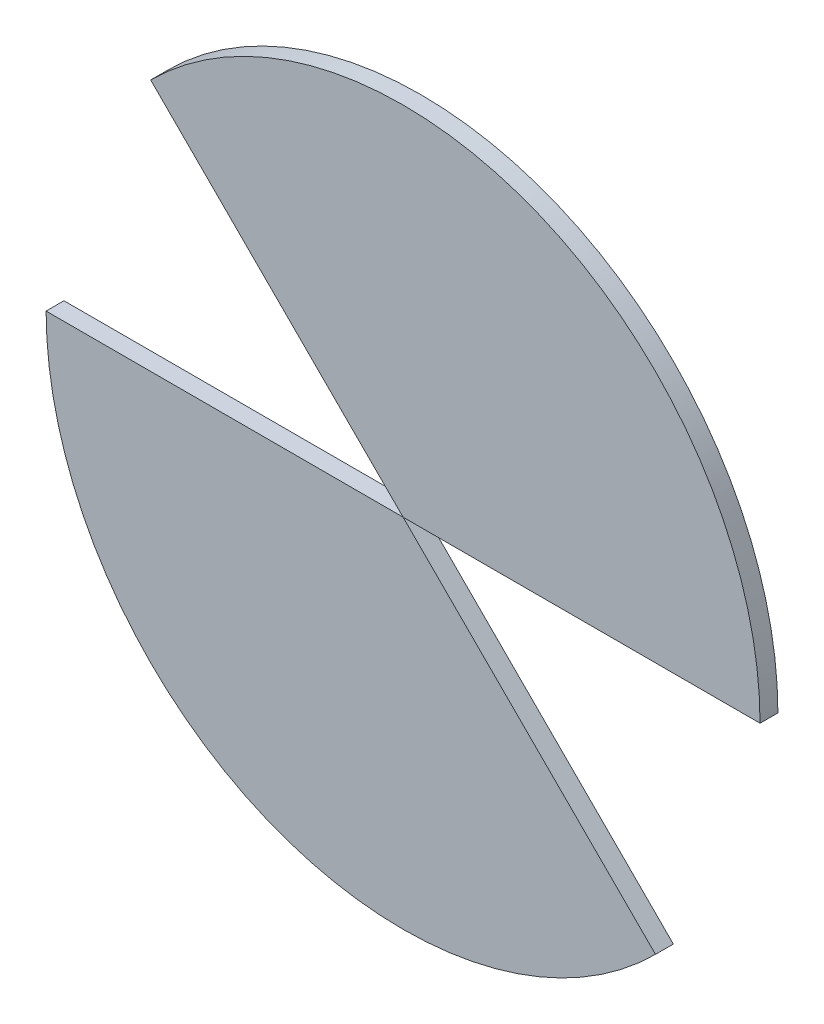
SolidWorks part; units mm, degrees
ref_plane "Front Plane" through (0, 0, 0) normal (0, 0, 1) x (1, 0, 0)
ref_plane "Top Plane" through (0, 0, 0) normal (0, 1, 0) x (1, 0, 0)
ref_plane "Right Plane" through (0, 0, 0) normal (1, 0, 0) x (0, 0, -1)
sketch "Sketch1" plane through (0, 0, 0) normal (0, 0, 1) x (1, 0, 0)
  line L1 (0, 0) -> (-100, 0)
  line L2 (70.7107, -70.7107) -> (0, 0)
  arc A3 (-100, 0) -> (70.7107, -70.7107) centre (0, 0) ccw
  dimension "D1" = 100
  dimension "D2" = 45
  dimension "D3" = 0
extrude "Boss-Extrude1" add sketch "Sketch1" along normal blind 5
ref_axis "Axis1" through (0, 0, 32.0444) along (0, 0, -1)
sketch "Sketch2" plane through (0, 0, 0) normal (0, 0, 1) x (1, 0, 0)
  line L0 (0, 0) -> (100, 0)
  line L1 (-70.7107, 70.7107) -> (0, 0)
  line L2 (0, 0) -> (-100, 0) construction
  arc A0 (100, 0) -> (-70.7107, 70.7107) centre (0, 0) ccw
  dimension "D1" = 45
  dimension "D2" = 100
extrude "Boss-Extrude2" add sketch "Sketch2" along normal up to surface (5 mm away) separate body up to face at (-17.6377, -42.5811, 5)
